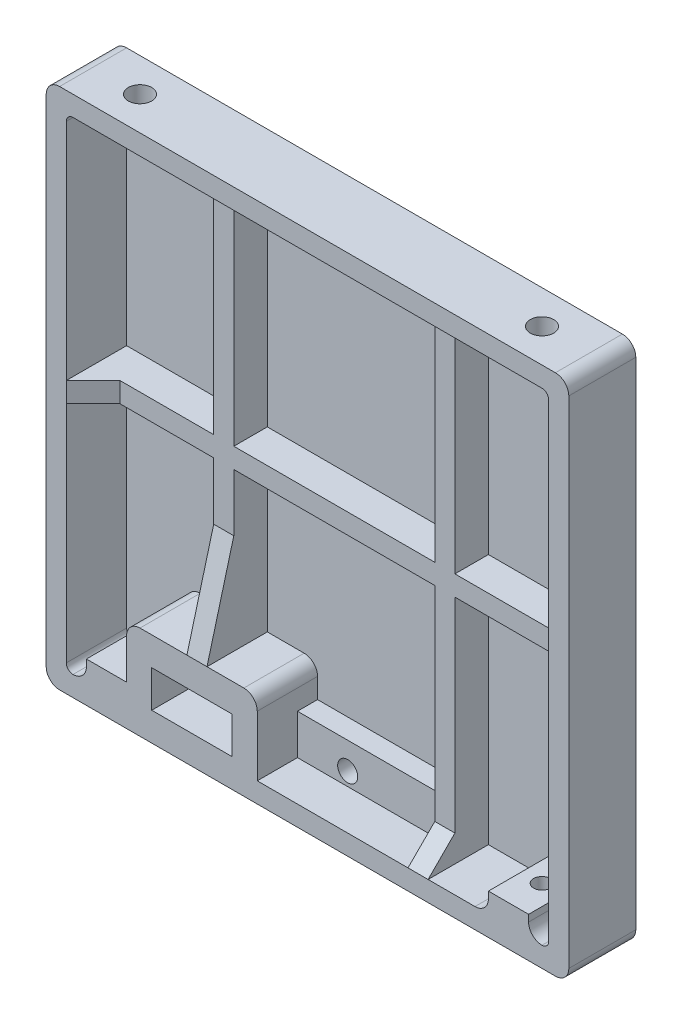
SolidWorks part; units mm, degrees
ref_plane "Front Plane" through (0, 0, 0) normal (0, 0, 1) x (1, 0, 0)
ref_plane "Top Plane" through (0, 0, 0) normal (0, 1, 0) x (1, 0, 0)
ref_plane "Right Plane" through (0, 0, 0) normal (1, 0, 0) x (0, 0, -1)
sketch "Sketch1" plane through (0, 0, 0) normal (0, 0, 1) x (1, 0, 0)
  line L1 (-39, -39) -> (39, -39)
  line L2 (-39, -39) -> (-39, 39)
  line L3 (-39, 39) -> (39, 39)
  line L4 (39, -39) -> (39, 39)
  line L5 (-39, -39) -> (39, 39) construction
  line L6 (-39, 39) -> (39, -39) construction
  point P0 (0, 0)
  dimension "D1" = 78
  dimension "D2" = 78
extrude "Boss-Extrude1" add sketch "Sketch1" along normal blind 10
sketch "Sketch9" plane through (0, 0, 10) normal (0, 0, 1) x (1, 0, 0)
  line L0 (-39, 39) -> (-39, -39) construction
  line L6 (-39, 16) -> (-34, 16)
  line L7 (-39, 16) -> (-39, 14)
  line L8 (-39, 14) -> (-34, 14)
  line L9 (-34, 16) -> (-34, 14)
  point P10 (-39, 15)
  dimension "D1" = 5
  dimension "D2" = 2
  dimension "D3" = 15
extrude "Cut-Extrude6" [suppressed] cut sketch "Sketch9" against normal offset from surface (9 mm away) 1
mirror "Mirror3" [suppressed] about plane through (0, 0, 0) normal (0, 1, 0)
ref_axis "Axis1" [suppressed] through (0, 0, 10.5) along (0, 0, -1)
pattern_circular "CirPattern1" [suppressed] count 4 over 360 about axis through (0, 0, 10.5) along (0, 0, -1) of bodies 119
shell "Shell1" thickness 3 removed face at (0, 0, 10)
sketch "Sketch10" plane through (0, 0, 0) normal (0, 1, 0) x (1, 0, 0)
  line L0 (39, 0) -> (-39, 0) construction
  circle A0 centre (-30, -5) radius 1.25
  dimension "D3" = 2.5
  dimension "D1" = 30
  dimension "D2" = 5
extrude "Cut-Extrude7" cut sketch "Sketch10" against normal through all both and the other way through all
mirror "Mirror4" about plane through (0, 0, 0) normal (1, 0, 0) of "Cut-Extrude7"
fillet "Fillet1" [suppressed] radius 1
fillet "Fillet2" [suppressed] radius 2
fillet "Fillet5" radius 2 4 edges at (39, 39, 5) (39, -39, 5) (-39, -39, 5) (-39, 39, 5)
fillet "Fillet6" radius 1 4 edges at (36, 36, 5.5) (-36, 36, 5.5) (-36, -36, 5.5) (36, -36, 5.5)
fillet "Fillet4" [suppressed] radius 1
sketch "Sketch15" plane through (0, -36, 0) normal (0, 1, 0) x (1, 0, 0)
  line L0 (-35, -1) -> (35, -1) construction
  line L1 (-33, -1) -> (-27, -1)
  line L2 (-33, -1) -> (-33, -10)
  line L3 (-33, -10) -> (-27, -10)
  line L4 (-27, -1) -> (-27, -10)
  line L5 (-35, -10) -> (35, -10) construction
  line L6 (-30, -5) -> (-30, -10) construction
  circle A0 centre (-30, -5) radius 1.25 construction
  circle A1 centre (-30, -5) radius 1.25
  dimension "D1" = 6
extrude "Boss-Extrude2" add sketch "Sketch15" along normal blind 3
fillet "Fillet7" radius 2 2 edges at (-27, -36, 5.5) (-33, -36, 5.5)
mirror "Mirror5" about plane through (0, 0, 0) normal (1, 0, 0) of "Fillet7", "Boss-Extrude2"
sketch "Sketch16" plane through (0, 36, 0) normal (0, -1, 0) x (1, 0, 0)
  circle A0 centre (-30, 5) radius 1.75
  circle A1 centre (30, 5) radius 1.75
  dimension "D1" = 3.5
extrude "Cut-Extrude9" cut sketch "Sketch16" against normal through all
sketch "Sketch17" plane through (0, 0, 1) normal (0, 0, 1) x (1, 0, 0)
  line L0 (0, 36) -> (-36, 0)
  line L1 (35, 36) -> (-35, 36) construction
  line L2 (-36, 35) -> (-36, -35) construction
  line L3 (-36, 0) -> (-10, -36)
  line L4 (-25, -36) -> (25, -36) construction
  dimension "D1" = 10
extrude "Extrude-Thin1" [suppressed] add sketch "Sketch17" along normal blind 3 thin thin type one direction wall 1.5
mirror "Mirror6" [suppressed] about plane through (0, 0, 0) normal (1, 0, 0)
sketch "Sketch18" [suppressed] plane through (0, 0, 1) normal (0, 0, 1) x (1, 0, 0)
  line L0 (-18.5, 18.5) -> (18.5, 18.5)
  line L1 (0, 37) -> (-37, 0) construction
  line L2 (0, 37) -> (37, 0) construction
  line L3 (18.5, 18.5) -> (23.5, -18.5)
  line L4 (37, 0) -> (10, -37) construction
  line L5 (23.5, -18.5) -> (-23.5, -18.5)
  line L6 (-37, 0) -> (-10, -37) construction
  line L7 (-23.5, -18.5) -> (-18.5, 18.5)
extrude "Extrude-Thin2" [suppressed] add sketch "Sketch18" along normal up to surface (3 mm away) thin thin type mid plane wall 1.5
sketch "Sketch20" plane through (0, 0, 0) normal (0, 0, -1) x (-1, 0, 0)
  line L0 (25, -36) -> (-25, -36) construction
  line L1 (27, -36) -> (7.5, -36)
  line L2 (27, -36) -> (27, -25)
  line L3 (27, -25) -> (7.5, -25)
  line L4 (7.5, -36) -> (7.5, -25)
  line L5 (37, -39) -> (-37, -39) construction
  dimension "D1" = 14
  dimension "D2" = 19.5
extrude "Boss-Extrude3" add sketch "Sketch20" against normal up to surface (10 mm away) up to face at (0, 0, 10)
sketch "Sketch21" plane through (0, 0, 10) normal (0, 0, 1) x (1, 0, 0)
  line L0 (-17.25, -25) -> (-17.25, -39) construction
  line L1 (-25.25, -36.75) -> (-9.25, -36.75)
  line L2 (-25.25, -36.75) -> (-25.25, -27.25)
  line L3 (-25.25, -27.25) -> (-9.25, -27.25)
  line L4 (-9.25, -36.75) -> (-9.25, -27.25)
  line L5 (-25.25, -36.75) -> (-9.25, -27.25) construction
  line L6 (-25.25, -27.25) -> (-9.25, -36.75) construction
  line L8 (-7.5, -25) -> (-27, -25) construction
  line L9 (-37, -39) -> (37, -39) construction
  point P0 (-17.25, -32)
  dimension "D1" = 16
  dimension "D2" = 9.5
extrude "Cut-Extrude10" cut sketch "Sketch21" against normal through all from offset 1.5 offset against normal yes
sketch "Sketch22" plane through (0, 0, 8.5) normal (0, 0, -1) x (-1, 0, 0)
  line L14 (11.25, -34.75) -> (23.25, -34.75)
  line L15 (23.25, -34.75) -> (23.25, -29.25)
  line L16 (11.25, -29.25) -> (11.25, -34.75)
  line L17 (23.25, -29.25) -> (11.25, -29.25)
  line L18 (11.25, -34.75) -> (23.25, -34.75)
  line L19 (23.25, -34.75) -> (23.25, -29.25)
  line L20 (11.25, -29.25) -> (11.25, -34.75)
  line L21 (23.25, -29.25) -> (11.25, -29.25)
  dimension "D1" = 2
extrude "Cut-Extrude11" cut sketch "Sketch22" against normal through all
extrude "Extrude-Thin3" add sketch "Sketch22<2>" along normal up to surface (8.5 mm away) thin up to face at (-17.25, -32, 0) thin type one direction wall 0.5
sketch "Sketch22<2>" plane through (0, 0, 8.5) normal (0, 0, -1) x (-1, 0, 0) same geometry as "Sketch22"
fillet "Fillet8" radius 2 2 edges at (-7.5, -25, 5.5) (-27, -25, 5.5)
sketch "Sketch26" plane through (0, 0, 1) normal (0, 0, 1) x (1, 0, 0)
  line L0 (-7.5, -27) -> (-7.5, -36) construction
  line L1 (-7.5, -30) -> (15, -30)
  line L2 (-7.5, -30) -> (-7.5, -36)
  line L3 (-7.5, -36) -> (15, -36)
  line L4 (15, -30) -> (15, -36)
  line L5 (-7.5, -36) -> (25, -36) construction
  dimension "D1" = 6
  dimension "D2" = 15
extrude "Boss-Extrude4" add sketch "Sketch26" along normal blind 3
sketch "Sketch13" plane through (0, 0, 0) normal (0, 0, 1) x (1, 0, 0)
  line L0 (-37, -39) -> (37, -39) construction
  circle A0 centre (0, -34) radius 1.5
  dimension "D1" = 3
  dimension "D2" = 5
extrude "Cut-Extrude8" cut sketch "Sketch13" along normal through all
sketch "Sketch28" plane through (0, 0, 1) normal (0, 0, 1) x (1, 0, 0)
  line L0 (-9.5, -25) -> (-25, -25) construction
  line L1 (-18, -25) -> (-15, -25)
  line L2 (-18, -25) -> (-18, 36)
  line L3 (-18, 36) -> (-15, 36)
  line L4 (-15, -25) -> (-15, 36)
  line L5 (35, 36) -> (-35, 36) construction
  line L6 (15, -36) -> (25, -36) construction
  line L7 (15, -36) -> (18, -36)
  line L8 (15, -36) -> (15, 36)
  line L9 (15, 36) -> (18, 36)
  line L10 (18, -36) -> (18, 36)
  dimension "D1" = 3
  dimension "D2" = 15
  dimension "D3" = 15
extrude "Boss-Extrude5" add sketch "Sketch28" along normal blind 5
sketch "Sketch29" plane through (0, 0, 1) normal (0, 0, 1) x (1, 0, 0)
  line L0 (-36, 35) -> (-36, -35) construction
  line L1 (-36, 1.5) -> (36, 1.5)
  line L2 (-36, 1.5) -> (-36, -1.5)
  line L3 (-36, -1.5) -> (36, -1.5)
  line L4 (36, 1.5) -> (36, -1.5)
  line L5 (36, -35) -> (36, 35) construction
  line L6 (0, 1.5) -> (0, -1.5) construction
  dimension "D1" = 3
extrude "Boss-Extrude6" add sketch "Sketch29" along normal up to surface (5 mm away) up to face at (16.5, 0, 6)
chamfer "Chamfer1" distance 4 angle 75 1 edges at (-16.5, -25, 6) first distance on face at (-16.875, -25, 4.5)
chamfer "Chamfer2" distance 4 angle 45 5 edges at (16.5, 36, 6) (-16.5, 36, 6) (36, 0, 6) (16.5, -36, 6) (-36, 0, 6)
